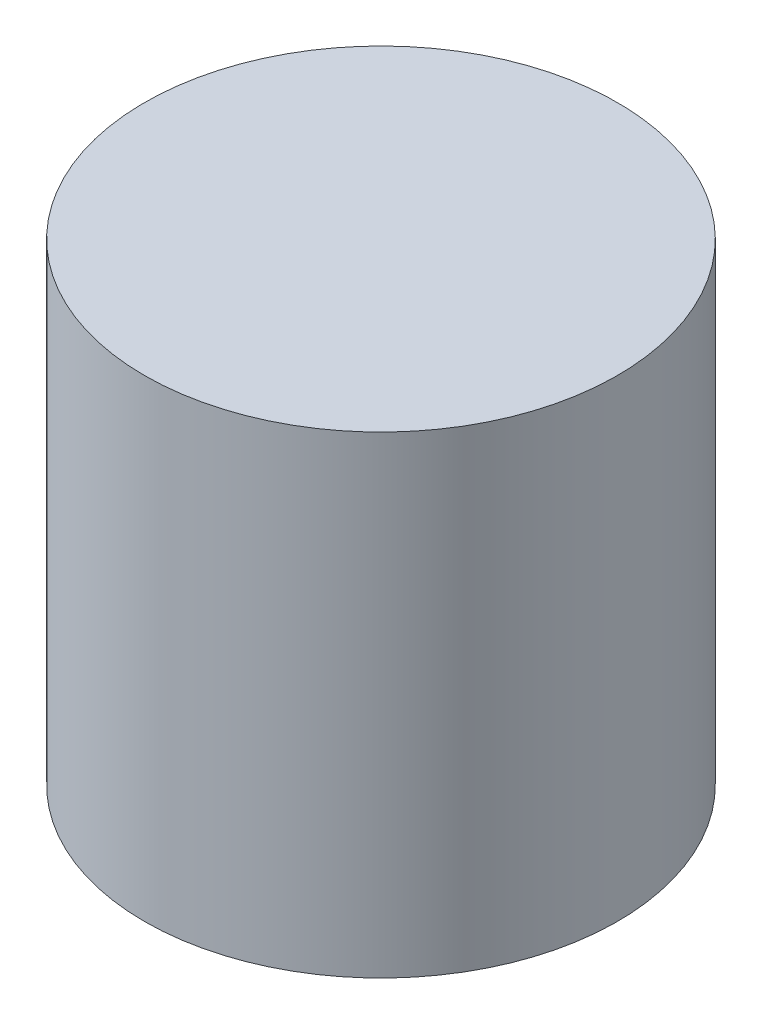
SolidWorks part; units mm, degrees
ref_plane "Front Plane" through (0, 0, 0) normal (0, 0, 1) x (1, 0, 0)
ref_plane "Top Plane" through (0, 0, 0) normal (0, 1, 0) x (1, 0, 0)
ref_plane "Right Plane" through (0, 0, 0) normal (1, 0, 0) x (0, 0, -1)
ref_plane "Plane1" through (0, -150, 0) normal (0, 1, 0) x (1, 0, 0)
ref_plane "Plane2" through (0, 0, -500) normal (0, 0, 1) x (1, 0, 0)
ref_plane "Plane4" through (250, 0, 0) normal (1, 0, 0) x (0, 0, -1)
ref_axis "Axis1" through (250, -150, -338.99) along (0, 0, 1)
ref_point "Point1"
ref_plane "Plane3" through (0, -150, 0) normal (0, 1, 0) x (1, 0, 0)
sketch "Sketch1" plane through (0, -150, 0) normal (0, 1, 0) x (1, 0, 0)
  circle A0 centre (250, 500) radius 75
  dimension "D1" = 150
extrude "Boss-Extrude1" add sketch "Sketch1" along normal up to surface (150 mm away) up to plane "Top Plane"
ref_axis "Axis2" through (250, -157.5, -500) along (0, 1, 0)
ref_plane "approach" through (279.0064, 0, -483.2532) normal (-0.5, 0, 0.866) x (0, 1, 0)
